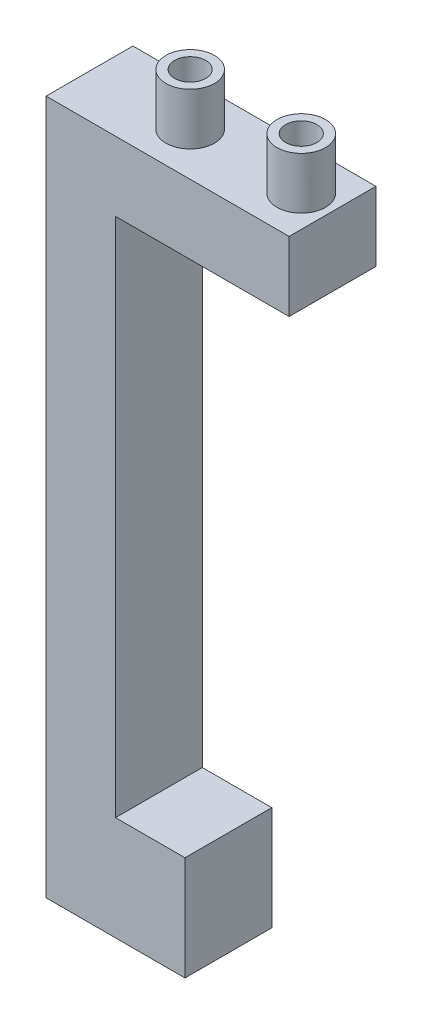
SolidWorks part; units mm, degrees
ref_plane "Piano frontale" through (0, 0, 0) normal (0, 0, 1) x (1, 0, 0)
ref_plane "Piano superiore" through (0, 0, 0) normal (0, 1, 0) x (1, 0, 0)
ref_plane "Piano destro" through (0, 0, 0) normal (1, 0, 0) x (0, 0, -1)
sketch "Schizzo2" plane through (0, 0, 0) normal (0, 0, 1) x (1, 0, 0)
  line L0 (0, 0) -> (-70, 0)
  line L1 (-70, 0) -> (-70, -200)
  line L2 (-70, -200) -> (-30, -200)
  line L3 (-30, -200) -> (-30, -170)
  line L4 (-30, -170) -> (-50, -170)
  line L5 (-50, -170) -> (-50, -20)
  line L6 (-50, -20) -> (0, -20)
  line L7 (0, -20) -> (0, 0)
  dimension "D1" = 70
  dimension "D2" = 50
  dimension "D3" = 200
  dimension "D4" = 20
  dimension "D5" = 30
  dimension "D6" = 20
extrude "Estrusione-Estrusione1" add sketch "Schizzo2" along normal blind 25
sketch "Schizzo3" plane through (0, 0, 0) normal (0, 1, 0) x (1, 0, 0)
  line L0 (0, -12.5) -> (-9, -12.5) construction
  line L1 (0, -25) -> (0, 0) construction
  line L2 (-9, -12.5) -> (-41, -12.5) construction
  circle A0 centre (-41, -12.5) radius 7
  circle A1 centre (-9, -12.5) radius 7
  dimension "D3" = 14
  dimension "D4" = 14
  dimension "D1" = 9
  dimension "D2" = 32
extrude "Estrusione-Estrusione2" add sketch "Schizzo3" along normal blind 14.91
hole_wizard "Foro lamato per Vite M8 a testa cilindrica-1" positions "Schizzo4" profile "Schizzo5" counterbore size "M8" standard "ISO" end condition through all
sketch "Schizzo4" plane through (0, -20, 0) normal (0, -1, 0) x (-1, 0, 0)
  line L0 (0, -12.5) -> (9, -12.5) construction
  line L1 (0, -25) -> (0, 0) construction
  line L2 (9, -12.5) -> (41, -12.5) construction
  point P0 (9, -12.5)
  point P2 (41, -12.5)
  point P13 (0, 0)
  point P14 (0, 0)
  dimension "D1" = 9
  dimension "D2" = 32
sketch "Schizzo5" plane through (-9, -20, 12.5) normal (1, 0, 0) x (0, 0, -1)
  line L0 (0, 0) -> (0, 34.91)
  line L1 (0, 34.91) -> (4.5, 34.91)
  line L3 (4.5, 34.91) -> (4.5, 8.6)
  line L4 (4.5, 8.6) -> (7.5, 8.6)
  line L5 (7.5, 8.6) -> (7.5, 0)
  line L7 (7.5, 0) -> (0, 0)
  line L11 (0, -6.35) -> (0, 107.95) construction
  dimension "Thru Hole Dia." = 9
  dimension "Thru Hole Depth" = 34.91
  dimension "C'Bore Dia." = 15
  dimension "C'Bore Depth" = 8.6
